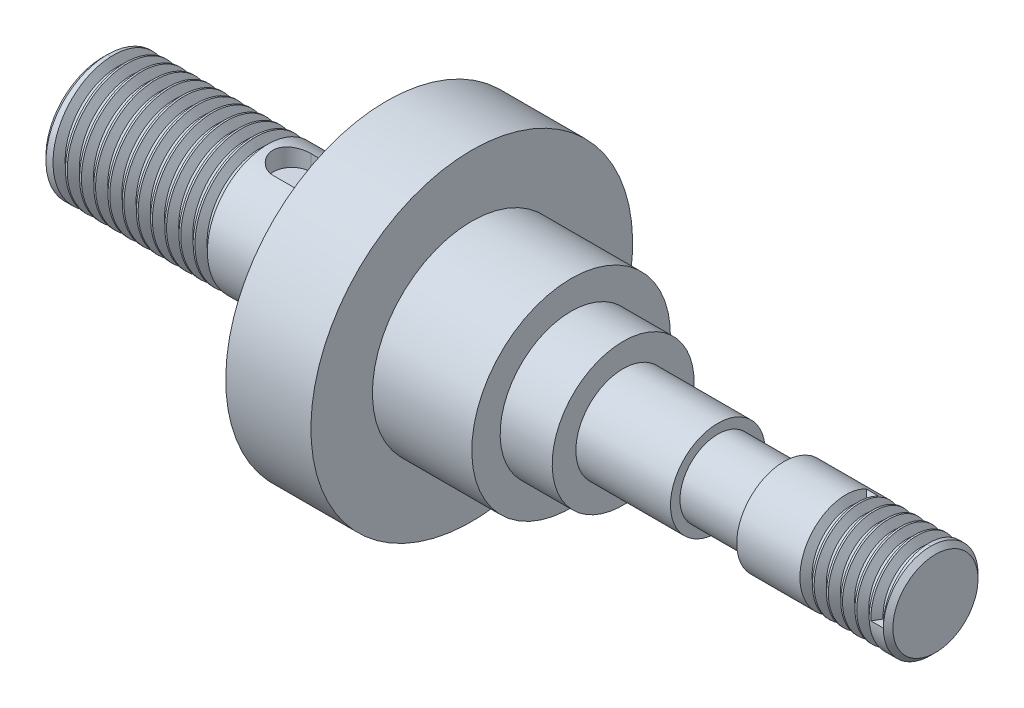
SolidWorks part; units mm, degrees
ref_plane "Front Plane" through (0, 0, 0) normal (0, 0, 1) x (1, 0, 0)
ref_plane "Top Plane" through (0, 0, 0) normal (0, 1, 0) x (1, 0, 0)
ref_plane "Right Plane" through (0, 0, 0) normal (1, 0, 0) x (0, 0, -1)
sketch "Sketch1" plane through (0, 0, 0) normal (0, 0, 1) x (1, 0, 0)
  line L1 (0, 3) -> (60, 3)
  line L2 (60, 3) -> (60, 24)
  line L3 (60, 24) -> (78, 24)
  line L4 (78, 24) -> (78, 11)
  line L5 (78, 11) -> (99, 11)
  line L6 (99, 11) -> (99, 5)
  line L7 (99, 5) -> (110, 5)
  line L8 (110, 5) -> (110, 0)
  line L9 (110, 0) -> (130, 0)
  line L10 (130, 0) -> (130, -2)
  line L11 (130, -2) -> (144, -2)
  line L12 (144, -2) -> (144, 0)
  line L13 (144, 0) -> (176, 0)
  line L14 (176, 0) -> (176, -10)
  line L15 (176, -10) -> (0, -10) construction
  line L16 (0, -10) -> (0, 3)
  line L17 (0, -10) -> (176, -10)
  dimension "D1" = 176
  dimension "D2" = 20
  dimension "D3" = 16
  dimension "D4" = 30
  dimension "D5" = 42
  dimension "D6" = 68
  dimension "D7" = 26
  dimension "D8" = 60
  dimension "D9" = 32
  dimension "D10" = 46
  dimension "D11" = 20
  dimension "D12" = 20
  dimension "D13" = 77
  dimension "D14" = 98
revolve "Revolve1" add sketch "Sketch1" angle 360 about L15
sketch "Sketch2" plane through (0, 0, 0) normal (0, 1, 0) x (1, 0, 0)
  line L0 (40, 0) -> (52, 0) construction
  line L1 (40, 4) -> (52, 4)
  line L2 (40, -4) -> (52, -4)
  arc A0 (40, 4) -> (40, -4) centre (40, 0) ccw
  arc A1 (52, -4) -> (52, 4) centre (52, 0) ccw
  point P3 (46, 0)
  point P8 (36, 0)
  point P9 (56, 0)
  dimension "D1" = 12
  dimension "D2" = 20
  dimension "D3" = 40
extrude "Cut-Extrude2" cut sketch "Sketch2" along normal blind 3 and the other way blind 1
chamfer "Chamfer2" distance 1 angle 45 2 edges at (176, 0, 0) (0, 3, 0)
thread "Thread3" pitch 3 method cut profile "Thread Profile4" start angle 0, offset 0, length 33, pitch 3, diameter 26
ref_plane "Plane4" through (1, -10, -13) normal (0, -1, 0) x (0, 0, -1)
sketch "Thread Profile4" plane through (1, -10, -13) normal (0, -1, 0) x (0, 0, -1)
  line L0 (0, 0) -> (0, 3) construction
  line L11 (0, 0) -> (0, 2.625)
  line L12 (0, 2.625) -> (-1.6238, 1.6875)
  line L13 (-1.6238, 1.6875) -> (-1.6238, 0.9375)
  line L15 (-1.6238, 0.9375) -> (0, 0)
  line L17 (-1.6238, 1.3125) -> (0, 1.3125) construction
  point P2 (0, 0)
  dimension "Pitch" = 3
  dimension "Profile_Angle" = 60
  dimension "Profile_Land" = 0.75
  dimension "Profile_Height" = 1.6238
thread "Thread4" pitch 3 method cut profile "Thread Profile5" start angle 0, offset 0, length 16, pitch 3, diameter 20
ref_plane "Plane5" through (175, -10, 10) normal (0, -1, 0) x (0, 0, 1)
sketch "Thread Profile5" plane through (175, -10, 10) normal (0, -1, 0) x (0, 0, 1)
  line L0 (0, 0) -> (0, 3) construction
  line L11 (0, 0) -> (0, 2.625)
  line L12 (0, 2.625) -> (-1.6238, 1.6875)
  line L13 (-1.6238, 1.6875) -> (-1.6238, 0.9375)
  line L15 (-1.6238, 0.9375) -> (0, 0)
  line L17 (-1.6238, 1.3125) -> (0, 1.3125) construction
  point P2 (0, 0)
  dimension "Pitch" = 3
  dimension "Profile_Angle" = 60
  dimension "Profile_Land" = 0.75
  dimension "Profile_Height" = 1.6238
